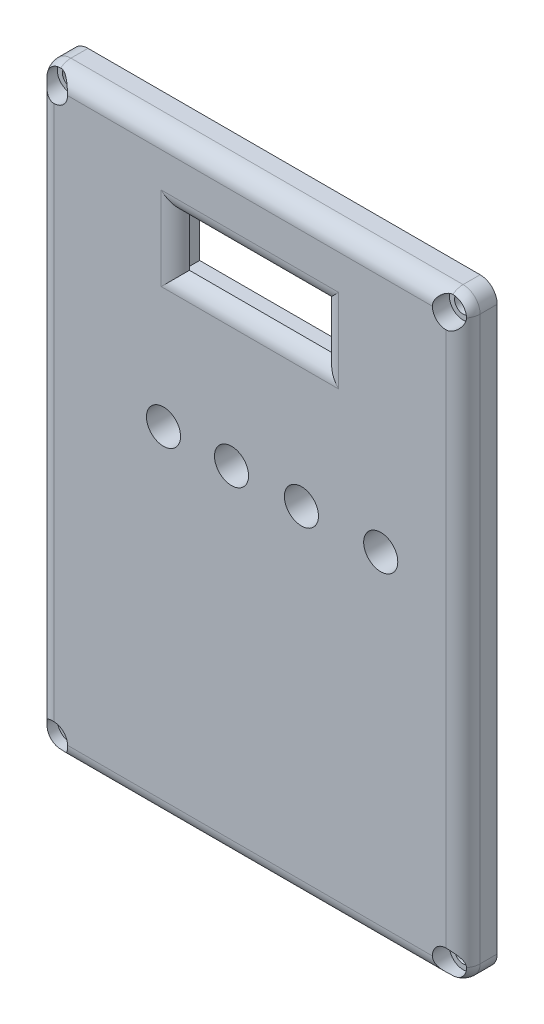
SolidWorks part; units mm, degrees
ref_plane "Front Plane" through (0, 0, 0) normal (0, 0, 1) x (1, 0, 0)
ref_plane "Top Plane" through (0, 0, 0) normal (0, 1, 0) x (1, 0, 0)
ref_plane "Right Plane" through (0, 0, 0) normal (1, 0, 0) x (0, 0, -1)
sketch "Sketch1" plane through (0, 0, 0) normal (0, 0, 1) x (1, 0, 0)
  line L1 (0, 0) -> (250, 0)
  line L2 (0, 0) -> (0, -350)
  line L3 (0, -350) -> (250, -350)
  line L4 (250, 0) -> (250, -350)
  line L5 (82.5, -40) -> (167.5, -40)
  line L6 (82.5, -40) -> (82.5, -70)
  line L7 (82.5, -70) -> (167.5, -70)
  line L8 (167.5, -40) -> (167.5, -70)
  circle A4 centre (74.3, -150) radius 10
  circle A5 centre (114.2, -150) radius 10
  circle A6 centre (155.2, -150) radius 10
  circle A7 centre (201.7, -150) radius 10
  dimension "D3" = 74.3
  dimension "D4" = 39.9
  dimension "D5" = 41
  dimension "D8" = 20
  dimension "D7" = 20
  dimension "D9" = 20
  dimension "D10" = 20
  dimension "D1" = 250
  dimension "D2" = 350
  dimension "D6" = 46.5
  dimension "D11" = 200
  dimension "D12" = 200
  dimension "D13" = 200
  dimension "D14" = 200
  dimension "D15" = 85
  dimension "D16" = 30
  dimension "D17" = 82.5
  dimension "D18" = 40
extrude "Boss-Extrude1" add sketch "Sketch1" against normal blind 20 contours L2 L1 L4 L3
sketch "Sketch2" plane through (0, 0, 0) normal (0, 0, 1) x (1, 0, 0)
  line L0 (0, 0) -> (0, -350) construction
  line L1 (82.5, -40) -> (167.5, -40)
  line L2 (82.5, -40) -> (82.5, -70)
  line L3 (82.5, -70) -> (167.5, -70)
  line L4 (167.5, -40) -> (167.5, -70)
  line L5 (0, 0) -> (250, 0) construction
  line L6 (0, -350) -> (250, -350) construction
  circle A1 centre (74.3, -150) radius 10
  circle A2 centre (114.2, -150) radius 10
  circle A3 centre (141.5596, -150) radius 10
  circle A4 centre (185.5376, -150) radius 10
  dimension "D1" = 30
  dimension "D5" = 200
  dimension "D6" = 74.3
  dimension "D2" = 85
  dimension "D3" = 82.5
  dimension "D4" = 40
  dimension "D7" = 39.9
extrude "Boss-Extrude2" add sketch "Sketch2" against normal blind 14 contours L2 L1 L4 L3
sketch "Sketch3" plane through (0, 0, 0) normal (0, 0, 1) x (1, 0, 0)
  line L0 (0, 0) -> (250, 0) construction
  line L1 (82.5, -40) -> (167.5, -40)
  line L2 (82.5, -40) -> (82.5, -70)
  line L3 (82.5, -70) -> (167.5, -70)
  line L4 (167.5, -40) -> (167.5, -70)
  line L5 (0, 0) -> (0, -350) construction
  dimension "D1" = 30
  dimension "D2" = 85
  dimension "D3" = 40
  dimension "D4" = 82.5
extrude "Cut-Extrude1" cut sketch "Sketch3" against normal blind 41 contours L2 L1 L4 L3
sketch "Sketch4" plane through (0, 0, -20) normal (0, 0, -1) x (-1, 0, 0)
  line L0 (-167.5, -40) -> (-82.5, -40) construction
  line L1 (-174.5, -35) -> (-75.5, -35)
  line L2 (-174.5, -35) -> (-174.5, -75)
  line L3 (-174.5, -75) -> (-75.5, -75)
  line L4 (-75.5, -35) -> (-75.5, -75)
  line L5 (-167.5, -70) -> (-82.5, -70) construction
  line L6 (-167.5, -70) -> (-167.5, -40) construction
  line L7 (-82.5, -70) -> (-82.5, -40) construction
  dimension "D1" = 5
  dimension "D2" = 5
  dimension "D3" = 7
  dimension "D4" = 7
extrude "Cut-Extrude2" cut sketch "Sketch4" against normal blind 5 contours L2 L1 L4 L3
sketch "Sketch5" plane through (0, 0, -15) normal (0, 0, -1) x (-1, 0, 0)
  line L2 (-174.5, -35) -> (-75.5, -35)
  line L3 (-174.5, -35) -> (-174.5, -75)
  line L4 (-174.5, -75) -> (-75.5, -75)
  line L5 (-75.5, -35) -> (-75.5, -75)
extrude "Cut-Extrude3" cut sketch "Sketch5" against normal blind 8
sketch "Sketch6" plane through (0, 0, 0) normal (0, 0, 1) x (1, 0, 0)
  line L0 (0, 0) -> (0, -350) construction
  line L1 (0, -350) -> (250, -350) construction
  circle A0 centre (74.3, -150) radius 10
  circle A1 centre (114.2, -150) radius 10
  circle A2 centre (155.2, -150) radius 10
  circle A3 centre (201.7, -150) radius 10
  point P12 (0, 0)
  point P14 (0, 0)
  dimension "D1" = 74.3
  dimension "D6" = 20
  dimension "D7" = 20
  dimension "D8" = 20
  dimension "D9" = 20
  dimension "D2" = 200
  dimension "D3" = 39.9
  dimension "D4" = 41
  dimension "D5" = 46.5
extrude "Cut-Extrude4" cut sketch "Sketch6" against normal blind 31 contours A0
sketch "Sketch7" plane through (0, 0, 0) normal (0, 0, 1) x (1, 0, 0)
  circle A0 centre (114.2, -150) radius 10
extrude "Cut-Extrude5" cut sketch "Sketch7" against normal blind 31
sketch "Sketch8" plane through (0, 0, 0) normal (0, 0, 1) x (1, 0, 0)
  circle A0 centre (155.2, -150) radius 10
extrude "Cut-Extrude6" cut sketch "Sketch8" against normal blind 31
sketch "Sketch9" plane through (0, 0, 0) normal (0, 0, 1) x (1, 0, 0)
  circle A0 centre (201.7, -150) radius 10
extrude "Cut-Extrude7" cut sketch "Sketch9" against normal blind 31
fillet "Fillet1" radius 10 1 edges at (125, 0, 0)
fillet "Fillet2" radius 10 3 edges at (0, 0, -15) (0, -2.9289, -2.9289) (0, -180, 0)
fillet "Fillet3" radius 10 3 edges at (250, 0, -15) (250, -2.9289, -2.9289) (250, -180, 0)
fillet "Fillet4" radius 10 5 edges at (0, -350, -15) (2.9289, -350, -2.9289) (250, -350, -15) (247.0711, -350, -2.9289) (125, -350, 0)
fillet "Fillet5" radius 10 1 edges at (125, -70, 0)
fillet "Fillet6" radius 10 1 edges at (82.5, -59.7697, 0)
fillet "Fillet7" radius 10 1 edges at (120.2303, -40, 0)
fillet "Fillet8" radius 10 1 edges at (167.5, -55, 0)
sketch "Sketch10" plane through (0, 0, 0) normal (0, 0, 1) x (1, 0, 0)
  circle A2 centre (240, -10) radius 8
extrude "Cut-Extrude8" cut sketch "Sketch10" against normal blind 10
sketch "Sketch11" plane through (0, 0, 0) normal (0, 0, 1) x (1, 0, 0)
  circle A0 centre (10, -10) radius 8
extrude "Cut-Extrude9" cut sketch "Sketch11" against normal blind 10
sketch "Sketch12" plane through (0, 0, 0) normal (0, 0, 1) x (1, 0, 0)
  circle A0 centre (10, -340) radius 8
extrude "Cut-Extrude10" cut sketch "Sketch12" against normal blind 10
sketch "Sketch13" plane through (0, 0, 0) normal (0, 0, 1) x (1, 0, 0)
  circle A0 centre (240, -340) radius 8
extrude "Cut-Extrude11" cut sketch "Sketch13" against normal blind 10
sketch "Sketch14" plane through (0, 0, -10) normal (0, 0, 1) x (1, 0, 0)
  circle A0 centre (10, -10) radius 5
extrude "Cut-Extrude12" cut sketch "Sketch14" against normal blind 10
sketch "Sketch15" plane through (0, 0, -10) normal (0, 0, 1) x (1, 0, 0)
  circle A0 centre (240, -10) radius 5
extrude "Cut-Extrude13" cut sketch "Sketch15" against normal blind 10
sketch "Sketch16" plane through (0, 0, -10) normal (0, 0, 1) x (1, 0, 0)
  circle A0 centre (240, -340) radius 5
extrude "Cut-Extrude14" cut sketch "Sketch16" against normal blind 10
sketch "Sketch17" plane through (0, 0, -10) normal (0, 0, 1) x (1, 0, 0)
  circle A0 centre (10, -340) radius 5
extrude "Cut-Extrude15" cut sketch "Sketch17" against normal blind 10
